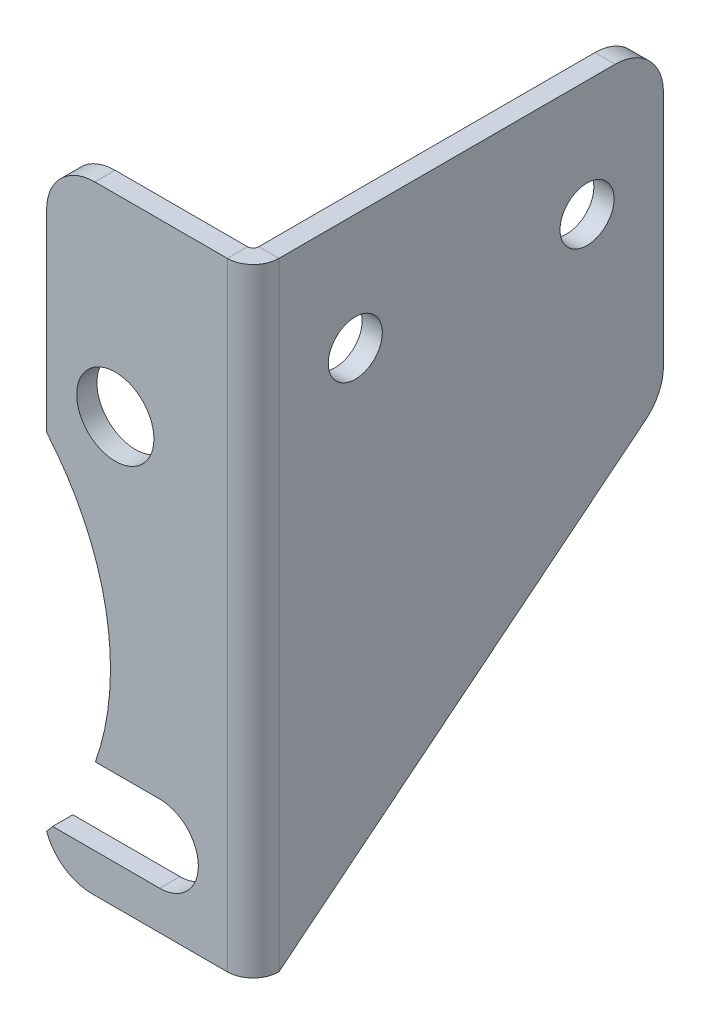
SolidWorks part; units mm, degrees
note: The reader was unsure of these and kept them because the rebuilt part matched: flange length of "Edge-Flange2".
ref_plane "Front" through (0, 0, 0) normal (0, 0, 1) x (1, 0, 0)
ref_plane "Top" through (0, 0, 0) normal (0, 1, 0) x (1, 0, 0)
ref_plane "Right" through (0, 0, 0) normal (1, 0, 0) x (0, 0, -1)
sketch "Sketch2" plane through (0, 0, 0) normal (0, 0, 1) x (1, 0, 0)
  line L0 (-11.8872, -36.5204) -> (-11.8872, -40.64)
  line L1 (-11.8872, 40.64) -> (11.8872, 40.64)
  line L2 (-11.8872, 40.64) -> (-11.8872, 8.936)
  line L3 (-11.8872, -40.64) -> (11.8872, -40.64)
  line L4 (11.8872, 40.64) -> (11.8872, -40.64)
  line L5 (2.9972, -25.4) -> (-5.4652, -25.4)
  line L6 (2.9972, -35.56) -> (-11.0933, -35.56)
  arc A0 (-11.8872, -36.5204) -> (-11.0933, -35.56) centre (-38.4048, -13.7922) ccw
  circle A1 centre (-2.8448, 15.24) radius 5.08
  arc A2 (2.9972, -35.56) -> (2.9972, -25.4) centre (2.9972, -30.48) ccw
  arc A3 (-5.4652, -25.4) -> (-11.8872, 8.936) centre (-38.4048, -13.7922) ccw
  point P4 (0, 40.64)
  point P6 (11.8872, 0)
  dimension "D3" = 45.72
  dimension "D7" = 10.16
  dimension "D10" = 69.85
  dimension "D1" = 81.28
  dimension "D2" = 23.7744
  dimension "D4" = 25.4
  dimension "D5" = 5.842
  dimension "D6" = 8.89
  dimension "D8" = 29.0322
  dimension "D9" = 35.56
base flange "Base-Flange2" sketch "Sketch2" thickness 2.6568 reverse thickness direction no parameters "D1"=0.7366
edge flange "Edge-Flange2" sketch "Sketch17" flange angle 90 flange length 53.975 flange position bend outside bend radius 0.7366 thickness 2.6568 relief rectangular parameters "D6"=10
sketch "Sketch17" plane through (11.8872, 0, -2.6568) normal (1, 0, 0) x (0, -1, 0)
  line L0 (40.64, 0) -> (-40.64, 0) construction
  line L1 (40.64, 0) -> (-40.64, 0)
  line L2 (-40.64, 0) -> (-40.64, 51.3182)
  line L3 (-40.64, 51.3182) -> (40.64, 51.3182)
  line L4 (40.64, 51.3182) -> (40.64, 0)
bend "EdgeBend2" bend radius 0.7366 bend angle 90 parameters "D5"=1
sketch "Sketch18" plane through (15.2806, 0, 0) normal (1, 0, 0) x (0, 0, -1)
  line L0 (13.4442, 25.4) -> (43.9242, 25.4) construction
  line L1 (53.975, 40.64) -> (3.3934, 40.64) construction
  line L3 (53.975, -40.64) -> (53.975, 40.64) construction
  line L4 (53.975, 0) -> (53.975, -40.64)
  line L5 (53.975, -40.64) -> (3.3934, -40.64)
  line L6 (3.3934, -40.64) -> (53.975, 0)
  circle A0 centre (13.4442, 25.4) radius 3.556
  circle A1 centre (43.9242, 25.4) radius 3.556
  point P2 (28.6842, 25.4)
  point P7 (28.6842, 40.64)
  dimension "D3" = 7.112
  dimension "D1" = 30.48
  dimension "D2" = 15.24
extrude "Cut-Extrude1" cut sketch "Sketch18" against normal blind 2.6568 normal cut yes
fillet "Fillet1" radius 6.35 4 edges at (13.9522, 0, -53.975) (-11.8872, -40.64, -1.3284) (13.9522, 40.64, -53.975) (-11.8872, 40.64, -1.3284)
sketch "Bend-Lines3" [suppressed] plane through (0, 0, 0) normal (0, 1, 0) x (1, 0, 0)
sketch "Bounding-Box3" [suppressed] plane through (0, 0, 0) normal (0, 1, 0) x (1, 0, 0)
sheet metal parameters "Sheet-Metal3" thickness 2.6568 parameters "D1"=0.7366
flat pattern "Flat-Pattern3" [suppressed]
sketch "Bend-Lines4" plane through (0, 0, 0) normal (0, 1, 0) x (1, 0, 0)
sketch3d "Bounding-Box4" [suppressed]
  line L0 (-50.292, 54.4322, 0) -> (-50.292, -26.8478, 0) construction
  line L1 (-26.5176, 54.4322, 0) -> (-26.5176, -26.8478, 0) construction
  line L2 (-50.292, 54.4322, 0) -> (-26.5176, 54.4322, 0) construction
  line L3 (-50.292, -26.8478, 0) -> (-26.5176, -26.8478, 0) construction
sheet metal parameters "Sheet-Metal4" thickness 2.6568 parameters "D1"=0.7366
flat pattern "Flat-Pattern3"
sketch "Bend-Lines4" plane through (0, 0, 0) normal (0, 0, 1) x (1, 0, 0)
  line L0 (10.1156, -40.64) -> (10.1156, 40.64) construction
  line L1 (10.1156, -40.64) -> (10.1156, 40.64) construction
sketch3d "Bounding-Box4" [suppressed]
  line L0 (100.7238, 54.4322, 0) -> (100.7238, -26.8478, 0) construction
  line L1 (26.5176, 54.4322, 0) -> (26.5176, -26.8478, 0) construction
  line L2 (100.7238, 54.4322, 0) -> (26.5176, 54.4322, 0) construction
  line L3 (100.7238, -26.8478, 0) -> (26.5176, -26.8478, 0) construction
bend of the flat pattern "Flatten-<EdgeBend2>1"
sheet metal parameters "Sheet-Metal5" thickness 2.6568 parameters "D1"=0.7366
flat pattern "Flat-Pattern3"
sketch "Bend-Lines4" plane through (0, 0, 0) normal (0, 0, 1) x (1, 0, 0)
  line L0 (13.5091, -40.64) -> (13.5091, 40.64) construction
  line L1 (13.5091, -40.64) -> (13.5091, 40.64) construction
sketch3d "Bounding-Box4" [suppressed]
  line L0 (104.1173, -26.8478, 0) -> (104.1173, 54.4322, 0) construction
  line L1 (26.5176, -26.8478, 0) -> (26.5176, 54.4322, 0) construction
  line L2 (104.1173, -26.8478, 0) -> (26.5176, -26.8478, 0) construction
  line L3 (104.1173, 54.4322, 0) -> (26.5176, 54.4322, 0) construction
bend of the flat pattern "Flatten-<EdgeBend2>1"
